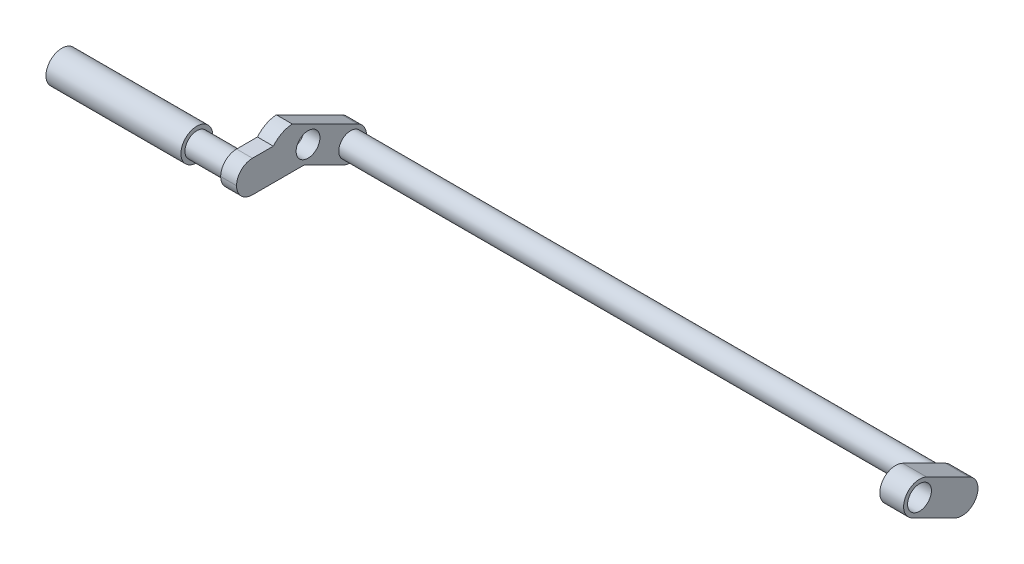
SolidWorks part; units mm, degrees
material "Nickel"
ref_plane "Front Plane" through (0, 0, 0) normal (0, 0, 1) x (1, 0, 0)
ref_plane "Top Plane" through (0, 0, 0) normal (0, 1, 0) x (1, 0, 0)
ref_plane "Right Plane" through (0, 0, 0) normal (1, 0, 0) x (0, 0, -1)
sketch "Sketch2" plane through (0, 0, 0) normal (1, 0, 0) x (0, 0, -1)
  circle A0 centre (0, 0) radius 2
  dimension "D1" = 4
extrude "Boss-Extrude1" add sketch "Sketch2" along normal blind 17
sketch "Sketch3" plane through (17, 0, 0) normal (1, 0, 0) x (0, 0, -1)
  circle A0 centre (0, 0) radius 1.5
  dimension "D1" = 3
extrude "Boss-Extrude2" add sketch "Sketch3" along normal blind 7
sketch "Sketch4" plane through (24, 0, 0) normal (1, 0, 0) x (0, 0, -1)
  line L1 (-2, 2) -> (1.9881, 2)
  line L2 (-2, 2) -> (-2, -2)
  line L3 (-2, -2) -> (1.9881, -2)
  line L4 (1.9881, 2) -> (1.9881, -2)
  circle A0 centre (0, 0) radius 2 construction
extrude "Boss-Extrude3" add sketch "Sketch4" against normal blind 2
sketch "Sketch5" plane through (0, 0, 2) normal (0, 0, 1) x (1, 0, 0)
  line L1 (24, 2) -> (22, 2)
  line L2 (24, 2) -> (24, -2)
  line L3 (24, -2) -> (22, -2)
  line L4 (22, 2) -> (22, -2)
extrude "Boss-Extrude4" add sketch "Sketch5" against normal blind 11
fillet "Fillet1" radius 2 1 edges at (23, 2, 2)
fillet "Fillet2" radius 2 1 edges at (23, -2, 2)
fillet "Fillet3" radius 2 2 edges at (23, -2, -9) (23, 2, -9)
sketch "Sketch6" plane through (24, 0, 0) normal (1, 0, 0) x (0, 0, -1)
  circle A0 centre (7, 0) radius 1.5
  dimension "D1" = 3
extrude "Cut-Extrude1" cut sketch "Sketch6" against normal through all
sketch "Sketch7" plane through (24, 0, 0) normal (1, 0, 0) x (0, 0, -1)
  line L0 (9, 0) -> (15.3922, -5.3637)
  line L1 (5.1606, -2) -> (12.8211, -8.4279)
  line L2 (0, -2) -> (7, -2) construction
  line L3 (5.1606, -2) -> (7, -2)
  line L4 (12.8211, -8.4279) -> (15.3922, -5.3637)
  line L6 (0, -2) -> (7, -2)
  line L7 (7, 2) -> (0, 2)
  line L8 (0, -2) -> (5.1606, -2)
  line L9 (7, 2) -> (0, 2)
  circle A0 centre (7, 0) radius 2
  arc A4 (7, -2) -> (9, 0) centre (7, 0) ccw
  arc A5 (9, 0) -> (7, 2) centre (7, 0) ccw
  arc A6 (0, 2) -> (-2, 0) centre (0, 0) ccw
  arc A7 (-2, 0) -> (0, -2) centre (0, 0) ccw
  arc A9 (9, 0) -> (7, 2) centre (7, 0) ccw
  arc A10 (0, 2) -> (-2, 0) centre (0, 0) ccw
  arc A11 (-2, 0) -> (0, -2) centre (0, 0) ccw
  line M11 (0, -2) -> (7, -2)
  arc M12 (7, -2) -> (9, 0) centre (7, 0) ccw
  dimension "D4" = 140
  dimension "D1" = 4
  dimension "D2" = 10
  dimension "D3" = 0
extrude "Boss-Extrude5" [suppressed] add sketch "Sketch7" against normal blind 2 contours L1 L4 L0 M12 M11
fillet "Fillet4" [suppressed] radius 2
fillet "Fillet5" [suppressed] radius 2
sketch "Sketch8" [suppressed] plane through (20, 0, 0) normal (1, 0, 0) x (0, 0, -1)
  circle A0 centre (16.5745, -5.6102) radius 1.5
  arc A1 (18.1066, -6.8958) -> (17.8601, -4.0781) centre (16.5745, -5.6102) ccw construction
  dimension "D1" = 3
extrude "Boss-Extrude6" [suppressed] add sketch "Sketch8" along normal blind 36
sketch "Sketch9" [suppressed] plane through (56, 0, 0) normal (1, 0, 0) x (0, 0, -1)
  line L0 (17.8601, -4.0781) -> (13, 0)
  line L1 (9.1606, -2) -> (15.289, -7.1423)
  line L2 (9.1606, -2) -> (9, 0)
  circle A0 centre (16.5745, -5.6102) radius 2
  circle A1 centre (11, 0) radius 2
  circle A2 centre (11, 0) radius 1.5
  circle M1 centre (16.5745, -5.6102) radius 1.5
  dimension "D1" = 3
extrude "Boss-Extrude7" [suppressed] add sketch "Sketch9" along normal blind 1.5 and the other way blind 1.5 contours A0 M1 | A1 L2 L1 A0 L0 | A1 L2 A2 | M1
sketch "Sketch10" plane through (24, 0, 0) normal (1, 0, 0) x (0, 0, -1)
  line L0 (7, 2) -> (0, 2) construction
  line L1 (5.0053, 3.2321) -> (13.2613, -0.8922)
  line L2 (7, 0) -> (12.3675, -2.6814) construction
  line L3 (11.4737, -4.4705) -> (6.5282, -2)
  line L4 (0, -2) -> (7, -2) construction
  arc A0 (2.6289, 2) -> (5.0053, 3.2321) centre (5.2832, -0.2117) cw
  arc A1 (9, 0) -> (7, 2) centre (7, 0) ccw construction
  circle A2 centre (12.3675, -2.6814) radius 1.5
  circle A3 centre (12.3675, -2.6814) radius 2
  point P18 (0, 0)
  line M6 (0, -2) -> (7, -2)
  arc M7 (7, -2) -> (9, 0) centre (7, 0) ccw
  arc M8 (9, 0) -> (7, 2) centre (7, 0) ccw
  line M9 (7, 2) -> (0, 2)
  dimension "D1" = 3
  dimension "D2" = 4
  dimension "D3" = 6
extrude "Boss-Extrude8" add sketch "Sketch10" against normal blind 2 contours L2 A3 L1 M7 M8 | L2 L3 A3 M7 M6 | A0 L1 M9 M8 | A3 A2 | A2 region at (24, -0.2975, -10.2049) region at (24, 2.4505, -4.8706) region at (24, -1.2627, -12.7021) region at (24, -1.6593, -14.0205) region at (24, -2.3852, -9.1704)
sketch "Sketch11" plane through (24, 0, 0) normal (1, 0, 0) x (0, 0, -1)
  circle A0 centre (12.3675, -2.6814) radius 1.5
  arc A1 (11.4737, -4.4705) -> (13.2613, -0.8922) centre (12.3675, -2.6814) ccw construction
  dimension "D1" = 3
extrude "Boss-Extrude9" add sketch "Sketch11" along normal blind 74
sketch "Sketch13" plane through (98, 0, 0) normal (1, 0, 0) x (0, 0, -1)
  line L0 (6.1062, -1.7892) -> (11.4737, -4.4705)
  line L1 (7.8938, 1.7892) -> (13.2613, -0.8922)
  circle A0 centre (12.3675, -2.6814) radius 2
  circle A1 centre (7, 0) radius 2
  circle A2 centre (7, 0) radius 1.5
  circle A3 centre (12.3675, -2.6814) radius 1.5
  circle M5 centre (12.3675, -2.6814) radius 1.5
extrude "Boss-Extrude10" add sketch "Sketch13" along normal blind 3 contours A1 A2 | A0 M5 | A1 L0 A0 L1 | M5 region at (98, -1.3407, -9.6838) region at (98, 0.8685, -5.2614) region at (98, -1.8129, -10.629) region at (98, -2.6814, -12.3675)
